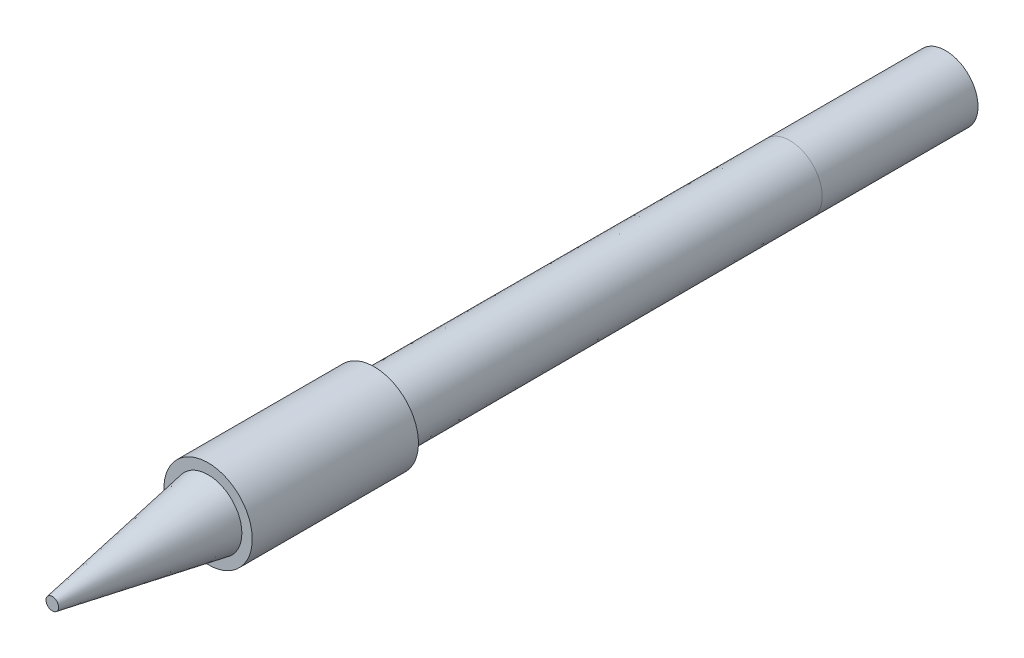
SolidWorks part; units mm, degrees
ref_plane "前视基准面" through (0, 0, 0) normal (0, 0, 1) x (1, 0, 0)
ref_plane "上视基准面" through (0, 0, 0) normal (0, 1, 0) x (1, 0, 0)
ref_plane "右视基准面" through (0, 0, 0) normal (1, 0, 0) x (0, 0, -1)
other "Configuration Table"
sketch "Sketch1" plane through (0, 0, 0) normal (0, 0, 1) x (1, 0, 0)
  circle A0 centre (0, 0) radius 6.225
extrude "Boss-Extrude1" add sketch "Sketch1" along normal blind 80 draft 0.08 draft outward yes
extrude "Boss-Extrude2" add sketch "Sketch1<2>" against normal blind 30
sketch "Sketch1<2>" plane through (0, 0, 0) normal (0, 0, 1) x (1, 0, 0) same geometry as "Sketch1"
sketch "Sketch2" plane through (0, 0, 80) normal (0, 0, 1) x (1, 0, 0)
  circle A0 centre (0, 0) radius 8.5
extrude "Boss-Extrude3" add sketch "Sketch2" along normal blind 32
sketch "Sketch3" plane through (0, 0, 112) normal (0, 0, 1) x (1, 0, 0)
  circle A0 centre (0, 0) radius 6.5
extrude "Boss-Extrude4" add sketch "Sketch3" along normal blind 30 draft 10
